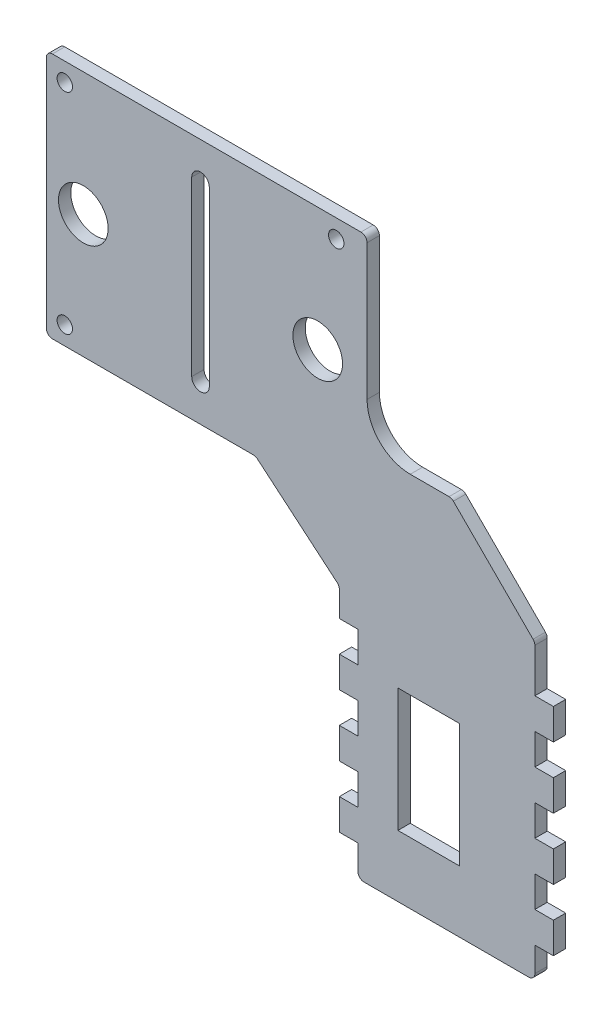
SolidWorks part; units mm, degrees
ref_plane "Front Plane" through (0, 0, 0) normal (0, 0, 1) x (1, 0, 0)
ref_plane "Top Plane" through (0, 0, 0) normal (0, 1, 0) x (1, 0, 0)
ref_plane "Right Plane" through (0, 0, 0) normal (1, 0, 0) x (0, 0, -1)
sketch "Sketch1" plane through (0, 0, 0) normal (0, 0, 1) x (1, 0, 0)
  line L0 (33.9359, 0) -> (47, -11)
  line L1 (0, 0) -> (50, 0)
  line L2 (0, 0) -> (0, 40)
  line L3 (0, 40) -> (50, 40)
  line L4 (50, 0) -> (50, 40)
  line L5 (50, 0) -> (79.2, 0)
  line L6 (50, 0) -> (50, -51)
  line L7 (50, -51) -> (79.2, -51)
  line L8 (79.2, 0) -> (79.2, -51)
  line L9 (50, 0) -> (79.2, 0)
  line L12 (79.2, 0) -> (79.2, -21)
  line L13 (79.2, 0) -> (50, 0)
  line L14 (79.2, 0) -> (79.2, 10)
  line L15 (79.2, 10) -> (50, 10)
  line L16 (50, 0) -> (50, 10)
  line L17 (40, 0) -> (50, 0)
  line L18 (40, 0) -> (40, -5)
  line L19 (40, -5) -> (50, -5)
  line L20 (50, 0) -> (50, -5)
  line L21 (50, -5) -> (44, -5)
  line L22 (50, -5) -> (50, -11)
  line L23 (50, -11) -> (44, -11)
  line L24 (44, -5) -> (44, -11)
  line L26 (50, 10) -> (52, 10)
  line L27 (50, 10) -> (50, 40)
  line L28 (50, 40) -> (52, 40)
  line L29 (52, 10) -> (52, 40)
  dimension "D1" = 50
  dimension "D2" = 40
  dimension "D3" = 29.2
  dimension "D4" = 51
  dimension "D5" = 0
  dimension "D6" = 10
  dimension "D7" = 0
  dimension "D8" = 0
  dimension "D9" = 0
  dimension "D10" = 10
  dimension "D11" = 5
  dimension "D12" = 0
  dimension "D13" = 0
  dimension "D14" = 6
  dimension "D15" = 6
  dimension "D16" = 2
  dimension "D17" = 3
extrude "plate_body" add sketch "Sketch1" along normal blind 2 contours L1 L4 L3 L2 | L8 L5 L1 L6 L7 | L14 L15 L4 L5 | L18 L19 L6 L1 | L19 L6 | L15 L29 L28 L4 | L18 L1 L0 | L24 L19 L0 region at (39.4486, -3.1115, 0) region at (25, 20, 0) region at (47.2353, -7.7462, 0) region at (45, -2.5, 0) region at (64.6, 5, 0) region at (64.6, -25.5, 0) region at (51, 25, 0)
sketch "Sketch2" plane through (0, 0, 2) normal (0, 0, 1) x (1, 0, 0)
  line L2 (0, 0) -> (0, 40) construction
  line L3 (0, 40) -> (52, 40) construction
  circle A0 centre (6, 20) radius 4.0238
  circle A1 centre (44, 20) radius 4.0238
  dimension "D1" = 38
  dimension "D2" = 8.0476
  dimension "D3" = 8.0476
  dimension "D4" = 6
  dimension "D5" = 20
  dimension "D6" = 20
extrude "shaft_bearings" cut sketch "Sketch2" against normal through all
sketch "Sketch4" plane through (0, 0, 2) normal (0, 0, 1) x (1, 0, 0)
  line L0 (25, 34) -> (25, 6) construction
  line L1 (26.425, 34) -> (26.425, 6)
  line L2 (23.575, 34) -> (23.575, 6)
  line L3 (0, 0) -> (33.9359, 0) construction
  line L5 (0, 0) -> (0, 40) construction
  arc A0 (26.425, 34) -> (23.575, 34) centre (25, 34) ccw
  arc A1 (23.575, 6) -> (26.425, 6) centre (25, 6) ccw
  point P2 (25, 20)
  dimension "D4" = 6
  dimension "D1" = 2.85
  dimension "D2" = 28
  dimension "D3" = 25
extrude "slot" cut sketch "Sketch4" against normal through all
sketch "Sketch5" plane through (0, 0, 2) normal (0, 0, 1) x (1, 0, 0)
  line L0 (0, 40) -> (52, 40) construction
  line L1 (0, 0) -> (0, 40) construction
  line L2 (52, 10) -> (52, 40) construction
  line L4 (0, 0) -> (33.9359, 0) construction
  circle A0 centre (3, 37) radius 1.25
  circle A1 centre (47, 37) radius 1.25
  circle A2 centre (3, 3) radius 1.25
  dimension "D1" = 2.5
  dimension "D2" = 2.5
  dimension "D3" = 2.5
  dimension "D4" = 5
  dimension "D5" = 3
  dimension "D6" = 3
  dimension "D7" = 3
  dimension "D8" = 3
  dimension "D12" = 3
extrude "bolt_holes" cut sketch "Sketch5" against normal through all
sketch "Sketch6" plane through (0, 0, 2) normal (0, 0, 1) x (1, 0, 0)
  line L0 (50, -51) -> (79.2, -51) construction
  line L1 (50, -11) -> (50.5, -11)
  line L2 (50, -11) -> (50, -51)
  line L3 (50, -51) -> (50.5, -51)
  line L4 (50.5, -11) -> (50.5, -51)
  line L5 (50, -11) -> (47, -11) construction
  dimension "D1" = 0.5
  dimension "D2" = 0
extrude "Cut-Extrude1" cut sketch "Sketch6" against normal through all
sketch "Sketch8" plane through (0, 0, 2) normal (0, 0, 1) x (1, 0, 0)
  line L0 (50.5, -36) -> (47.5, -36)
  line L1 (50.5, -46) -> (47.5, -46)
  line L2 (50.5, -46) -> (50.5, -41)
  line L3 (50.5, -41) -> (47.5, -41)
  line L4 (47.5, -46) -> (47.5, -41)
  line L5 (79.2, -46) -> (82.2, -46)
  line L6 (79.2, -46) -> (79.2, -41)
  line L7 (79.2, -41) -> (82.2, -41)
  line L8 (82.2, -46) -> (82.2, -41)
  line L9 (50.5, -36) -> (50.5, -31)
  line L10 (50.5, -31) -> (47.5, -31)
  line L11 (47.5, -36) -> (47.5, -31)
  line L12 (79.2, -36) -> (82.2, -36)
  line L13 (79.2, -36) -> (79.2, -31)
  line L14 (79.2, -31) -> (82.2, -31)
  line L15 (82.2, -36) -> (82.2, -31)
  line L16 (50.5, -51) -> (50.5, -11) construction
  line L17 (79.2, -51) -> (79.2, 10) construction
  line L18 (50.5, -16) -> (47.5, -16)
  line L19 (50.5, -26) -> (47.5, -26)
  line L20 (50.5, -26) -> (50.5, -21)
  line L21 (50.5, -21) -> (47.5, -21)
  line L22 (47.5, -26) -> (47.5, -21)
  line L23 (79.2, -26) -> (82.2, -26)
  line L24 (79.2, -26) -> (79.2, -21)
  line L25 (79.2, -21) -> (82.2, -21)
  line L26 (82.2, -26) -> (82.2, -21)
  line L27 (50.5, -16) -> (50.5, -11)
  line L28 (50.5, -11) -> (47.5, -11)
  line L29 (47.5, -16) -> (47.5, -11)
  line L30 (79.2, -16) -> (82.2, -16)
  line L31 (79.2, -16) -> (79.2, -11)
  line L32 (79.2, -11) -> (82.2, -11)
  line L33 (82.2, -16) -> (82.2, -11)
  line L34 (50.5, -51) -> (79.2, -51) construction
  point P38 (80.7, -31)
  point P41 (80.7, -41)
  dimension "D1" = 5
  dimension "D2" = 5
  dimension "D3" = 3
  dimension "D4" = 3
  dimension "D5" = 5
  dimension "D6" = 5
  dimension "D7" = 3
  dimension "D8" = 3
  dimension "D9" = 0
  dimension "D10" = 0
  dimension "D11" = 5
  dimension "D12" = 5
  dimension "D13" = 5
  dimension "D14" = 5
  dimension "D15" = 3
  dimension "D16" = 3
  dimension "D17" = 5
  dimension "D18" = 5
  dimension "D19" = 3
  dimension "D20" = 3
  dimension "D21" = 5
  dimension "D22" = 5
  dimension "D25" = 0
  dimension "D26" = 0
  dimension "D27" = 5
  dimension "D28" = 5
  dimension "D29" = 10
  dimension "D30" = 10
extrude "finger_joints" add sketch "Sketch8" along direction (0, 0, 1) on the side against the normal up to surface (2 mm away) up to face at (4.25, 3, 0)
sketch "Sketch9" plane through (0, 0, 2) normal (0, 0, 1) x (1, 0, 0)
  line L0 (50.5, -51) -> (79.2, -51) construction
  line L1 (57, -21) -> (67, -21)
  line L2 (57, -21) -> (57, -41)
  line L3 (57, -41) -> (67, -41)
  line L4 (67, -21) -> (67, -41)
  line L5 (50.5, -51) -> (50.5, -46) construction
  dimension "D1" = 10
  dimension "D2" = 20
  dimension "D3" = 10
  dimension "D4" = 6.5
extrude "gear_hole" cut sketch "Sketch9" against normal through all
sketch "Sketch10" plane through (0, 0, 2) normal (0, 0, 1) x (1, 0, 0)
  line L0 (0, 40) -> (52, 40) construction
  line L1 (9.3, 40) -> (24.3, 40)
  line L2 (9.3, 40) -> (9.3, 50)
  line L3 (9.3, 50) -> (24.3, 50)
  line L4 (24.3, 40) -> (24.3, 50)
  circle A0 centre (16.8, 45) radius 1.5
  arc A1 (26.425, 34) -> (23.575, 34) centre (25, 34) ccw construction
  point P11 (25, 35.425)
  dimension "D4" = 7.5
  dimension "D5" = 5
  dimension "D6" = 3
  dimension "D3" = 8.2
  dimension "D1" = 10
  dimension "D2" = 15
extrude "tail_rod_mount" [suppressed] add sketch "Sketch10" against normal up to surface (2 mm away)
sketch "Sketch12" plane through (0, 0, 2) normal (0, 0, 1) x (1, 0, 0)
  line L0 (65.7, 10) -> (79.2, -3.5)
  line L1 (79.2, 10) -> (65.7, 10)
  line L2 (79.2, 10) -> (79.2, -3.5)
  line L3 (79.2, -3.5) -> (65.7, -3.5)
  line L4 (65.7, 10) -> (65.7, -3.5)
  point P5 (79.2, 3.25)
  dimension "D1" = 13.5
  dimension "D2" = 13.5
extrude "Cut-Extrude3" cut sketch "Sketch12" against normal blind 10 contours L2 L1 L0 region at (74.7, 5.5, 2)
fillet "1mm_fillets" [suppressed] radius 1
fillet "7mm_fillet" [suppressed] radius 7
fillet "1mm_fillets_gear_hole" radius 1 9 edges at (79.2, -51, 1) (50.5, -51, 1) (47.5, -11, 1) (33.9359, 0, 1) (52, 40, 1) (0, 0, 1) (0, 40, 1) (79.2, -3.5, 1) (65.7, 10, 1)
fillet "7mm_fillet_gear_hole" radius 7 1 edges at (52, 10, 1)
